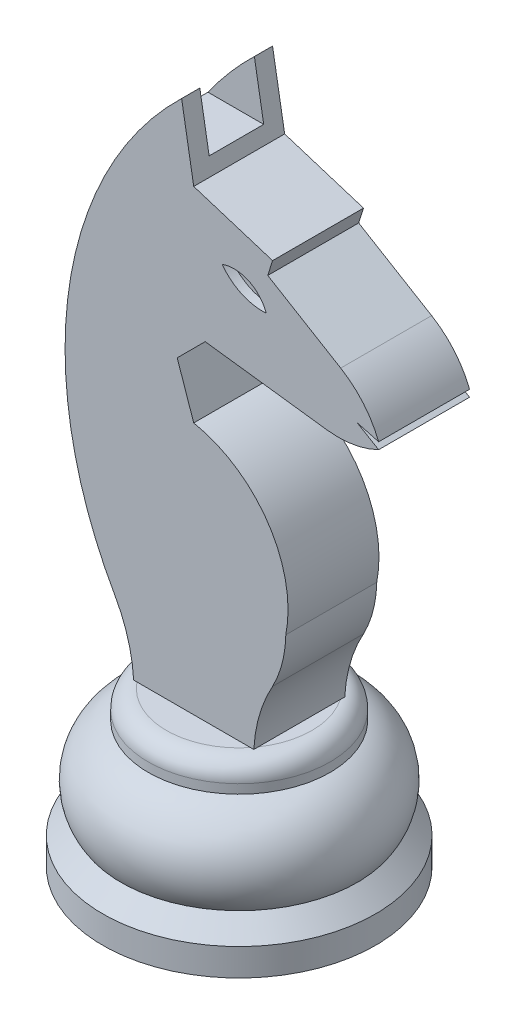
SolidWorks part; units mm, degrees
ref_plane "Front Plane" through (0, 0, 0) normal (0, 0, 1) x (1, 0, 0)
ref_plane "Top Plane" through (0, 0, 0) normal (0, 1, 0) x (1, 0, 0)
ref_plane "Right Plane" through (0, 0, 0) normal (1, 0, 0) x (0, 0, -1)
sketch "Sketch2" plane through (0, 0, 0) normal (0, 0, 1) x (1, 0, 0)
  line L0 (0, 0) -> (-15, 0)
  line L1 (0, 0) -> (0, 3)
  line L2 (0, 3) -> (0, 5)
  line L3 (0, 5) -> (0, 13.97)
  line L4 (0, 13.97) -> (0, 14.97)
  line L5 (0, 14.97) -> (0, 16.97)
  line L6 (0, 3) -> (-15, 3)
  line L7 (-15, 3) -> (-15, 0)
  line L9 (-13, 5) -> (-15, 3)
  line L12 (0, 16.97) -> (-8, 16.97)
  line L13 (-10, 13.97) -> (-10, 14.97)
  arc A0 (-13, 5) -> (-10, 13.97) centre (-7.9981, 8.3138) cw
  arc A1 (-10, 14.97) -> (-8, 16.97) centre (-8, 14.97) cw
  dimension "D11" = 6
  dimension "D1" = 15
  dimension "D2" = 3
  dimension "D3" = 2
  dimension "D4" = 8.97
  dimension "D5" = 1
  dimension "D6" = 2
  dimension "D7" = 13
  dimension "D8" = 10
  dimension "D9" = 10
  dimension "D10" = 8
revolve "Revolve1" add sketch "Sketch2" angle 360 about L3 region at (-7.5, 1.5, 0) region at (-6.3996, 9.506, 0)
sketch "Sketch3" plane through (0, 0, 0) normal (0, 0, 1) x (1, 0, 0)
  line L1 (8, 16.97) -> (-8, 16.97) construction
  line L3 (0, 67.29) -> (-1.33, 75)
  line L5 (-6.61, 16.97) -> (6.61, 16.97)
  line L7 (0, 67.29) -> (8.67, 64.56)
  line L8 (8.67, 64.56) -> (8.141, 62.88)
  line L9 (8.141, 62.88) -> (20.337, 55.57)
  line L10 (20.337, 55.57) -> (20.337, 53.1361)
  line L11 (20.337, 50.7022) -> (1.2604, 53.1361)
  line L12 (1.2604, 53.1361) -> (-1.8162, 50.0595)
  line L13 (-1.8162, 50.0595) -> (0, 44.7657)
  line L14 (20.337, 52.3819) -> (17.9834, 53.7733)
  line L15 (17.9834, 53.7733) -> (20.337, 53.1361)
  line L18 (20.337, 52.3819) -> (20.337, 50.7022)
  line L19 (8.67, 64.56) -> (0, 67.29)
  arc A0 (-6.61, 16.97) -> (-8.67, 24.01) centre (-22.6661, 16.0932) ccw
  arc A1 (-8.67, 24.01) -> (-1.33, 75) centre (27.9235, 44.7657) cw
  arc A2 (6.61, 16.97) -> (8.67, 24.01) centre (22.6661, 16.0932) cw
  arc A3 (8.67, 24.01) -> (10.13, 29.65) centre (-2.5471, 29.9227) ccw
  arc A4 (0, 44.7657) -> (10.13, 29.65) centre (-2.4928, 32.1428) cw
  point P0 (0, 0)
  dimension "D8" = 42.07
  dimension "D9" = 16.08
  dimension "D10" = 16.08
  dimension "D13" = 12.68
  dimension "D5" = 13.22
  dimension "D14" = 47.59
  dimension "D15" = 45.91
  dimension "D16" = 38.6
  dimension "D17" = 9.0897
extrude "Boss-Extrude1" add sketch "Sketch3" along normal mid plane 10 contours A4 L13 L12 L11 L18 L14 L15 L10 L9 L8 L7 L3 A1 A0 L5 A2 A3 region at (-0.8401, 43.9291, 0)
sketch "Sketch4" plane through (0, 0, 0) normal (1, 0, 0) x (0, 0, -1)
  line L1 (-3, 76.7246) -> (3, 76.7246)
  line L2 (-3, 76.7246) -> (-3, 69.0483)
  line L3 (-3, 69.0483) -> (3, 69.0483)
  line L4 (3, 76.7246) -> (3, 69.0483)
  dimension "D1" = 6
  dimension "D2" = 2
extrude "Cut-Extrude1" cut sketch "Sketch4" against normal blind 10
fillet "Fillet2" radius 10 1 edges at (20.337, 55.57, 0)
fillet "Fillet3" radius 10 1 edges at (20.337, 50.7022, 0)
sketch "Sketch5" plane through (0, 0, 0) normal (0, 0, 1) x (1, 0, 0)
  arc A0 (3.1237, 61.4367) -> (7.9831, 59.203) centre (7.572, 64.7111) ccw
  arc A1 (3.1237, 61.4367) -> (7.9831, 59.203) centre (4.4365, 57.8901) cw
extrude "Cut-Extrude2" cut sketch "Sketch5" against normal through all both and the other way through all contours A1 A0
extrude "Boss-Extrude2" add sketch "Sketch5<3>" along normal mid plane 8
sketch "Sketch5<3>" plane through (0, 0, 0) normal (0, 0, 1) x (1, 0, 0) same geometry as "Sketch5"
